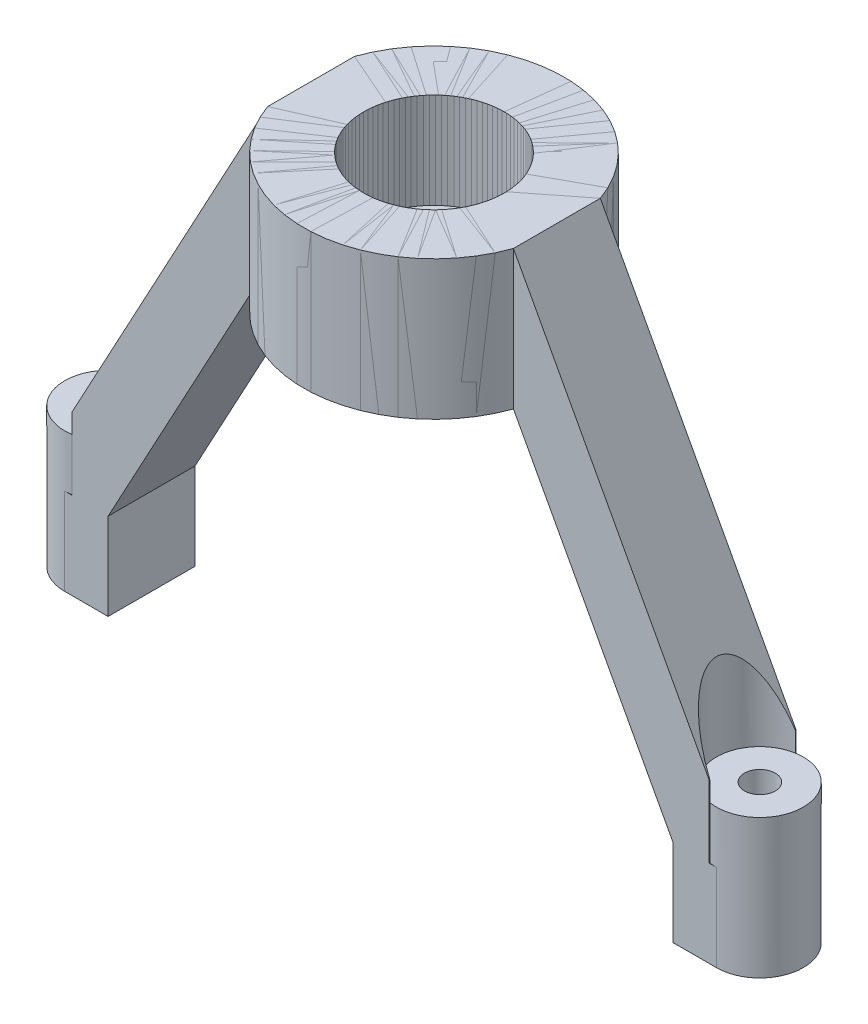
SolidWorks part; units mm, degrees
ref_plane "Front Plane" through (0, 0, 0) normal (0, 0, 1) x (1, 0, 0)
ref_plane "Top Plane" through (0, 0, 0) normal (0, 1, 0) x (1, 0, 0)
ref_plane "Right Plane" through (0, 0, 0) normal (1, 0, 0) x (0, 0, -1)
sketch "Sketch1" plane through (0, 0, 0) normal (0, 1, 0) x (1, 0, 0)
  line L2 (7.0711, 2.5) -> (7.0711, -2.5)
  line L4 (-26.3789, 0) -> (26.3789, 0) construction
  line L5 (-7.0711, 2.5) -> (-18.0711, 2.5) construction
  line L6 (7.0711, -2.5) -> (26.3789, -2.5) construction
  line L7 (0, 0) -> (0, 16.7972) construction
  line L11 (-7.0711, 2.5) -> (-7.0711, -2.5)
  arc A0 (-7.0711, -2.5) -> (7.0711, -2.5) centre (0, 0) ccw
  arc A1 (7.0711, 2.5) -> (-7.0711, 2.5) centre (0, 0) ccw
  circle A2 centre (-18.75, 0) radius 0.889
  circle A3 centre (0, 0) radius 1.875
  circle A8 centre (-18.75, 0) radius 2.5
  dimension "D3" = 15
  dimension "D5" = 3.75
extrude "Boss-Extrude1" add sketch "Sketch1" along normal blind 8 contours L2 A1 L11 A0 A3 region at (6.8649, 0, 0)
extrude "Boss-Extrude2" add sketch "Sketch1<3>" along normal blind 5 from offset 17 separate body contours A8 A2 region at (-21.1793, 0, 0) offset against normal yes
sketch "Sketch1<3>" plane through (0, 0, 0) normal (0, 1, 0) x (1, 0, 0) same geometry as "Sketch1"
sketch "Sketch3" plane through (0, 0, 0) normal (0, 0, 1) x (1, 0, 0)
  line L0 (-7.0711, 8) -> (-18.3373, -12.8659)
  line L1 (-18.3373, -12.8659) -> (-18.3373, -17)
  line L2 (-18.3373, -17) -> (-16.25, -17)
  line L3 (-16.25, -17) -> (-7.0711, 0)
  line L4 (-7.0711, 0) -> (-7.0711, 8)
sketch "Sketch4" plane through (0, 8, 0) normal (0, 1, 0) x (1, 0, 0)
  circle A0 centre (0, 0) radius 4.05
extrude "Cut-Extrude1" cut sketch "Sketch4" against normal blind 5.5
extrude "Boss-Extrude3" add sketch "Sketch3" along normal blind 2.5 and the other way blind 2.5
sketch "Sketch5" plane through (0, -12, 0) normal (0, 1, 0) x (1, 0, 0)
  circle A0 centre (-18.75, 0) radius 2.5
  circle A1 centre (-18.75, 0) radius 1.6841
  circle A4 centre (-18.75, 0) radius 2.5 construction
extrude "Cut-Extrude2" cut sketch "Sketch5" along normal through all and the other way blind 2 contours A0
sketch "Sketch8" plane through (0, -17, 0) normal (0, -1, 0) x (1, 0, 0)
  line L0 (-18.75, -2.5) -> (-16.25, -2.5)
  line L1 (-16.25, -2.5) -> (-16.25, 2.5)
  line L2 (-16.25, 2.5) -> (-18.75, 2.5)
  arc A0 (-18.75, 2.5) -> (-18.75, -2.5) centre (-18.75, 0) ccw
  circle A2 centre (-18.75, 0) radius 0.889
extrude "Boss-Extrude4" add sketch "Sketch8" along normal blind 5
extrude "Cut-Extrude3" cut sketch "Sketch1<4>" against normal through all contours A2 region at (-18.75, 0, 0)
sketch "Sketch1<4>" plane through (0, 0, 0) normal (0, 1, 0) x (1, 0, 0) same geometry as "Sketch1"
pattern_circular "CirPattern5" count 2 over 360 about axis through (0, 8, 0) along (0, 1, 0) of bodies 116 113
